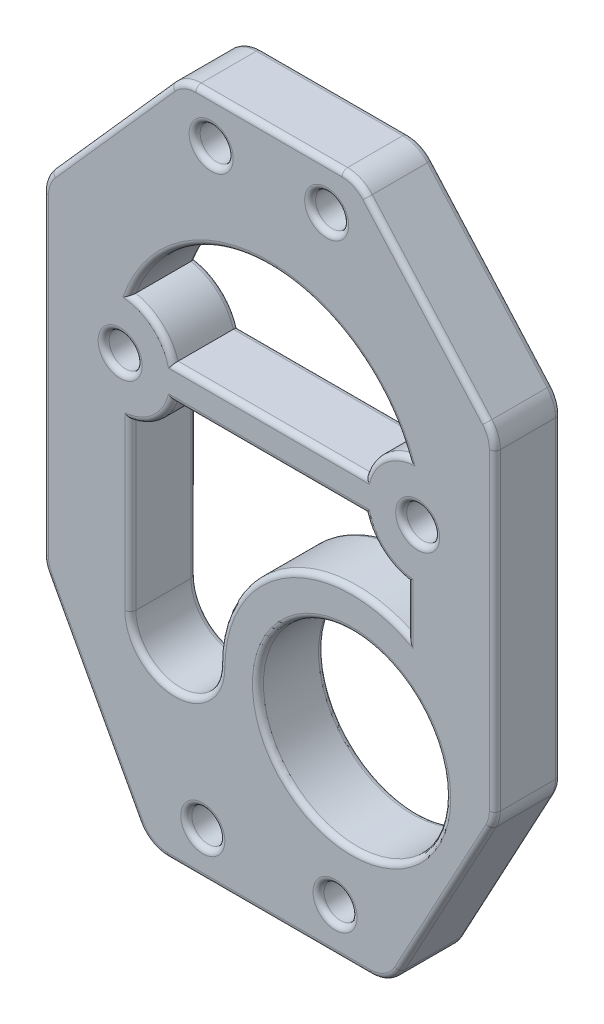
SolidWorks part; units mm, degrees
material "PET"
ref_plane "Front Plane" through (0, 0, 0) normal (0, 0, 1) x (1, 0, 0)
ref_plane "Top Plane" through (0, 0, 0) normal (0, 1, 0) x (1, 0, 0)
ref_plane "Right Plane" through (0, 0, 0) normal (1, 0, 0) x (0, 0, -1)
sketch "Sketch1" plane through (0, 0, 0) normal (0, 0, 1) x (1, 0, 0)
  line L0 (0, 0) -> (0, 62) construction
  line L1 (11, 0) -> (-11, 0)
  line L2 (-20.5, 17.5997) -> (-20.5, 47.8997)
  line L3 (-20.5, 47.8997) -> (-7.9898, 62)
  line L4 (-7.9898, 62) -> (7.9898, 62)
  line L5 (-11, 0) -> (-20.5, 17.5997)
  line L6 (11, 0) -> (20.5, 17.5997)
  line L7 (20.5, 17.5997) -> (20.5, 47.8997)
  line L8 (20.5, 47.8997) -> (7.9898, 62)
  line L9 (7.5, 17.5997) -> (20.5, 17.5997)
  line L10 (13.5, 37.5997) -> (-13.5, 37.5997) construction
  line L11 (12.5741, 32.6862) -> (12.5741, 28.4742)
  line L12 (-8.7303, 39.0997) -> (8.7303, 39.0997)
  line L13 (-8.7303, 39.0997) -> (-8.7303, 36.0997) construction
  line L14 (-8.7303, 36.0997) -> (8.7303, 36.0997)
  line L15 (8.7303, 39.0997) -> (8.7303, 36.0997) construction
  line L16 (-8.7303, 39.0997) -> (8.7303, 36.0997) construction
  line L17 (-8.7303, 36.0997) -> (8.7303, 39.0997) construction
  line L18 (-12.5741, 32.6862) -> (-12.5741, 17.5997)
  circle A0 centre (-5.2398, 58) radius 1.5
  circle A1 centre (-13.5, 37.5997) radius 1.5
  circle A2 centre (-6, 4) radius 1.5
  circle A3 centre (5.2398, 58) radius 1.5
  circle A4 centre (13.5, 37.5997) radius 1.5
  circle A5 centre (6, 4) radius 1.5
  circle A6 centre (7.5, 17.5997) radius 8.5
  circle A7 centre (13.5, 37.5997) radius 5 construction
  circle A8 centre (-13.5, 37.5997) radius 5 construction
  circle A9 centre (7.5, 17.5997) radius 12 construction
  arc A10 (-12.5741, 42.5132) -> (12.5741, 42.5132) centre (0, 37.5997) cw
  arc A11 (-8.7303, 39.0997) -> (-12.5741, 42.5132) centre (-13.5, 37.5997) ccw
  arc A12 (12.5741, 42.5132) -> (8.7303, 39.0997) centre (13.5, 37.5997) ccw
  arc A13 (-8.7303, 36.0997) -> (-12.5741, 32.6862) centre (-13.5, 37.5997) cw
  arc A14 (8.7303, 36.0997) -> (12.5741, 32.6862) centre (13.5, 37.5997) ccw
  arc A15 (-12.5741, 17.5997) -> (-4.5, 17.5997) centre (-8.537, 17.5997) ccw
  arc A16 (12.5741, 28.4742) -> (-4.5, 17.5997) centre (7.5, 17.5997) ccw
  point P34 (0, 51.0997)
  dimension "D2" = 6
  dimension "D13" = 13
  dimension "D14" = 3.5
  dimension "D17" = 13.5
  dimension "D1" = 62
  dimension "D3" = 4
  dimension "D4" = 11
  dimension "D5" = 20
  dimension "D6" = 30.3
  dimension "D7" = 10.3
  dimension "D8" = 7
  dimension "D9" = 2.75
  dimension "D10" = 4
  dimension "D11" = 18.85
  dimension "D12" = 20.5
  dimension "D18" = 3
  dimension "D15" = 3.5
  dimension "D16" = 3.5
extrude "Boss-Extrude2" add sketch "Sketch1" along normal blind 6 contours A6 L7 L8 L4 L3 L2 L5 L1 L6 A4 A0 A1 A2 A3 A5 A10 A12 L12 A11 L11 A16 A15 L18 A13 L14 A14 region at (0, 0.7433, 0)
fillet "Fillet1" radius 3 8 edges at (-20.5, 47.8997, 3) (-7.9898, 62, 3) (7.9898, 62, 3) (20.5, 47.8997, 3) (20.5, 17.5997, 3) (-20.5, 17.5997, 3) (-11, 0, 3) (11, 0, 3)
fillet "Fillet2" radius 0.5 68 edges at (1.0536, 27.7212, 0) (-8.537, 13.5627, 0) (-12.5741, 25.143, 0) (-10.1799, 33.8611, 0) (0, 36.0997, 0) (10.1799, 33.8611, 0) (12.5741, 30.5802, 0) (10.1799, 41.3383, 0) (0, 39.0997, 0) (-10.1799, 41.3383, 0) (0, 51.0997, 0) (7.5, 4, 0) (6.7398, 58, 0) (-4.5, 4, 0) (-12, 37.5997, 0) (-3.7398, 58, 0) (15, 37.5997, 0) (16, 17.5997, 0) (-20.4086, 17.6228, 0) (-15.9951, 9.2539, 0) (-10.7472, 0.4237, 0) (0, 0, 0) (10.7472, 0.4237, 0) (15.9951, 9.2539, 0) (20.4086, 17.6228, 0) (20.5, 32.5592, 0) (20.3047, 47.8256, 0) (14.3146, 54.8714, 0) (7.8712, 61.7361, 0) (0, 62, 0) (-7.8712, 61.7361, 0) (-14.3146, 54.8714, 0) (-20.3047, 47.8256, 0) (-20.5, 32.5592, 0) (10.1799, 33.8611, 6) (0, 36.0997, 6) (-10.1799, 33.8611, 6) (-12.5741, 25.143, 6) (-8.537, 13.5627, 6) (1.0536, 27.7212, 6) (12.5741, 30.5802, 6) (-10.1799, 41.3383, 6) (0, 39.0997, 6) (10.1799, 41.3383, 6) (0, 51.0997, 6) (7.5, 4, 6) (6.7398, 58, 6) (-4.5, 4, 6) (-12, 37.5997, 6) (-3.7398, 58, 6) (15, 37.5997, 6) (16, 17.5997, 6) (-7.8712, 61.7361, 6) (0, 62, 6) (7.8712, 61.7361, 6) (14.3146, 54.8714, 6) (20.3047, 47.8256, 6) (20.5, 32.5592, 6) (20.4086, 17.6228, 6) (15.9951, 9.2539, 6) (10.7472, 0.4237, 6) (0, 0, 6) (-10.7472, 0.4237, 6) (-15.9951, 9.2539, 6) (-20.4086, 17.6228, 6) (-20.5, 32.5592, 6) (-20.3047, 47.8256, 6) (-14.3146, 54.8714, 6)
